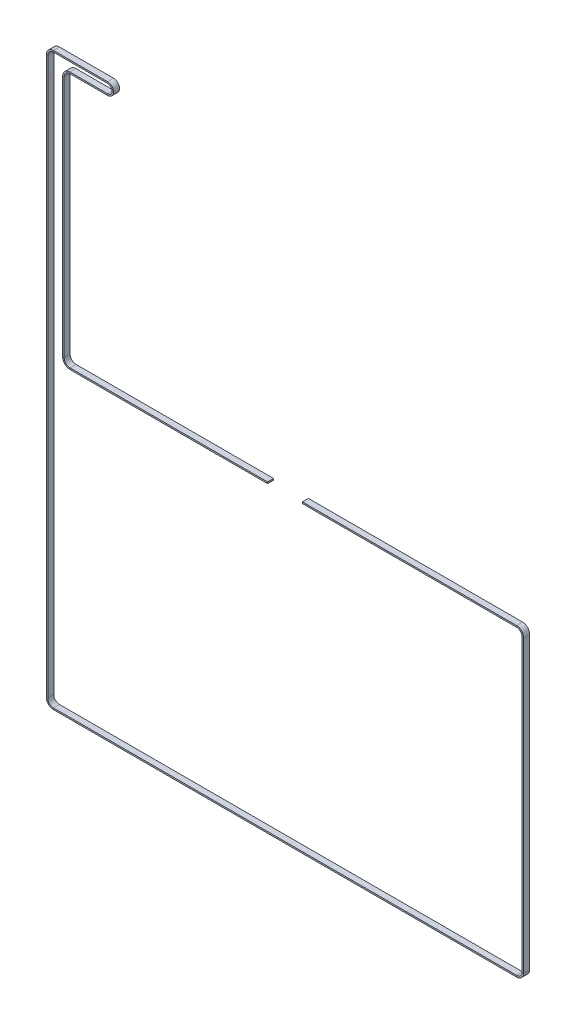
SolidWorks part; units mm, degrees
ref_plane "Front" through (0, 0, 0) normal (0, 0, 1) x (1, 0, 0)
ref_plane "Top" through (0, 0, 0) normal (0, 1, 0) x (1, 0, 0)
ref_plane "Right" through (0, 0, 0) normal (1, 0, 0) x (0, 0, -1)
sketch "Sketch1" plane through (0, -21, 4.45) normal (0, 0, 1) x (1, 0, 0)
  line L0 (10, 63.3) -> (47.5, 63.3)
  line L1 (47.5, 73.7) -> (-6.5, 73.7)
  line L2 (-12.875, 67.325) -> (-12.875, -488)
  line L3 (-6.5, -494.375) -> (455.5, -494.375)
  line L4 (461.875, -488) -> (461.875, -198.525)
  line L5 (455.5, -192.15) -> (241.85, -192.15)
  line L6 (207.15, -195.7) -> (207.15, -190.7) construction
  line L7 (3.4, 56.7) -> (3.4, -185.7)
  line L8 (10, -192.3) -> (207.15, -192.3)
  line L11 (241.85, -191.3) -> (241.85, -187.7) construction
  circle A0 centre (47.5, 68.5) radius 5.2 construction
  circle A1 centre (10, 56.7) radius 6.6 construction
  circle A2 centre (-6.5, 67.325) radius 6.375 construction
  circle A3 centre (10, -185.7) radius 6.6 construction
  circle A4 centre (-6.5, -488) radius 6.375 construction
  circle A5 centre (455.5, -488) radius 6.375 construction
  circle A6 centre (455.5, -198.525) radius 6.375 construction
  arc A7 (47.5, 73.7) -> (47.5, 63.3) centre (47.5, 68.5) cw
  arc A8 (10, 63.3) -> (3.4, 56.7) centre (10, 56.7) ccw
  arc A9 (-12.875, 67.325) -> (-6.5, 73.7) centre (-6.5, 67.325) cw
  arc A10 (-6.5, -494.375) -> (-12.875, -488) centre (-6.5, -488) cw
  arc A11 (455.5, -494.375) -> (461.875, -488) centre (455.5, -488) ccw
  arc A12 (461.875, -198.525) -> (455.5, -192.15) centre (455.5, -198.525) ccw
  arc A13 (3.4, -185.7) -> (10, -192.3) centre (10, -185.7) ccw
  circle A14 centre (-6.5, 67.325) radius 9 construction
  circle A15 centre (455.5, -198.525) radius 5.9875 construction
  circle A16 centre (10, -185.7) radius 5.9875 construction
  dimension "D1" = 12.75
ref_plane "Plane1" through (241.85, -213.15, 4.45) normal (-1, 0, 0) x (0, 0, 1)
sketch "Sketch2" plane through (241.85, -213.15, 4.45) normal (-1, 0, 0) x (0, 0, 1)
  line L1 (-3, 0.75) -> (3, 0.75)
  line L2 (-3, 0.75) -> (-3, -0.75)
  line L3 (-3, -0.75) -> (3, -0.75)
  line L4 (3, 0.75) -> (3, -0.75)
  line L5 (-3, 0.75) -> (3, -0.75) construction
  line L6 (-3, -0.75) -> (3, 0.75) construction
  point P0 (0, 0)
  dimension "D1" = 6
  dimension "D2" = 1.5
sweep "Sweep1" add profiles "Sketch2" path "Sketch1"
